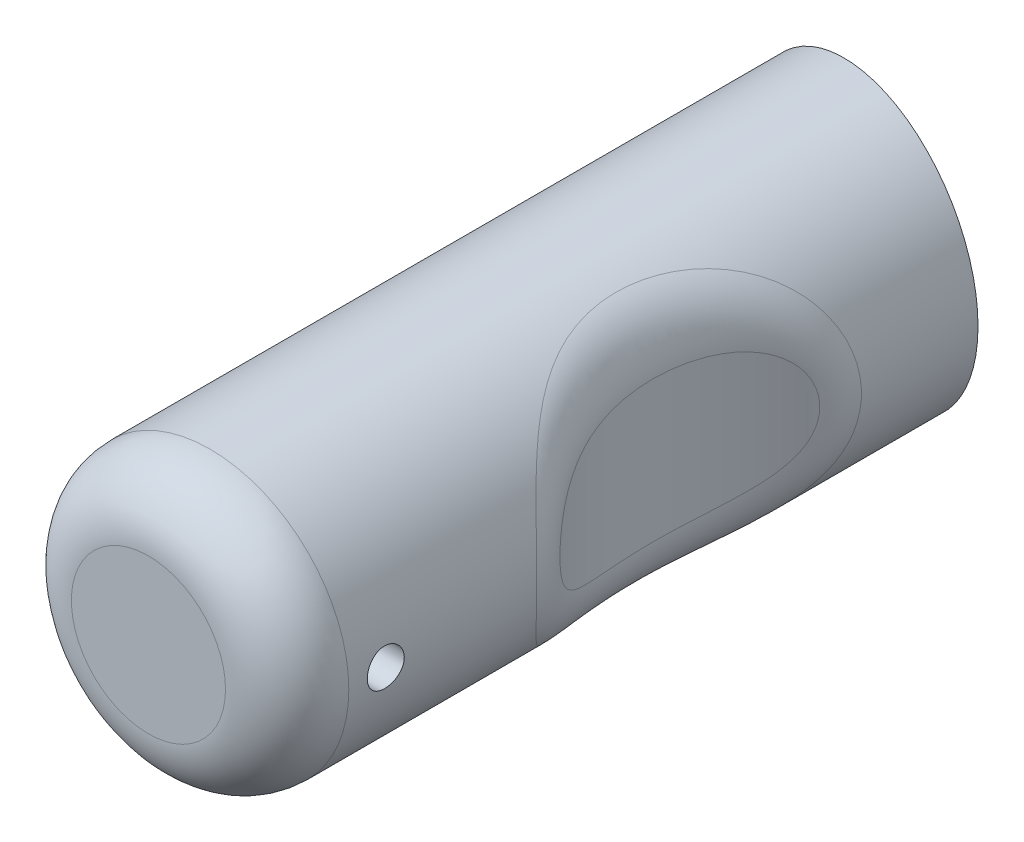
SolidWorks part; units mm, degrees
ref_plane "Front Plane" through (0, 0, 0) normal (0, 0, 1) x (1, 0, 0)
ref_plane "Top Plane" through (0, 0, 0) normal (0, 1, 0) x (1, 0, 0)
ref_plane "Right Plane" through (0, 0, 0) normal (1, 0, 0) x (0, 0, -1)
sketch "Sketch1" plane through (0, 0, 0) normal (0, 0, 1) x (1, 0, 0)
  circle A0 centre (0, 0) radius 22.5
  dimension "D1" = 45
extrude "Boss-Extrude1" add sketch "Sketch1" along normal blind 120
sketch "Sketch5" plane through (0, 0, 0) normal (0, 1, 0) x (1, 0, 0)
  line L0 (0, 0) -> (0, -120) construction
  line L1 (-22.5, -120) -> (22.5, -120) construction
  circle A0 centre (-30, -21.8566) radius 10
  circle A1 centre (-30, -61.8566) radius 10
  circle A2 centre (-30, -41.8566) radius 10
  circle A3 centre (-30, -81.8566) radius 10
  circle A4 centre (55, -53.1749) radius 40
  dimension "D1" = 20
  dimension "D3" = 20
  dimension "D4" = 20
  dimension "D5" = 55
  dimension "D6" = 30
  dimension "D2" = 20
extrude "Cut-Extrude5" cut sketch "Sketch5" against normal blind 124 and the other way blind 124 contours A2 | A0 | A1 | A3 | A4 region at (-30, 0, 21.8566) region at (-30, 0, 81.8566) region at (-30, 0, 61.8566) region at (-30, 0, 41.8566) region at (55, 0, 53.1749)
fillet "Fillet6" radius 10 1 edges at (22.5, 0, 120)
sketch "Sketch6" plane through (0, 0, 0) normal (0, 0, -1) x (-1, 0, 0)
  circle A0 centre (0, 0) radius 7.5
  dimension "D1" = 15
sketch "Sketch7" plane through (0, 0, 0) normal (1, 0, 0) x (0, 0, -1)
  line L0 (0, 0) -> (-110, 0) construction
  line L1 (-110, -22.5) -> (-110, 22.5) construction
  line L2 (-104, 22.5) -> (-104, -3) construction
  line L3 (0, 22.5) -> (-110, 22.5) construction
  circle A0 centre (-104, 0) radius 3
  dimension "D1" = 6
  dimension "D2" = 6
extrude "Cut-Extrude9" cut sketch "Sketch7" along normal blind 110
fillet "Fillet8" radius 10 5 edges at (22.3173, 2.8617, 30.1133) (-22.1484, -3.9619, 75.6636) (-22.1484, -3.9619, 55.6636) (-22.1484, -3.9619, 35.6636) (-22.1484, -3.9619, 15.6636)
sketch "Sketch9" plane through (0, 0, 0) normal (0, 1, 0) x (1, 0, 0)
  line L0 (-55.0338, 5.7366) -> (-53.8437, 18.2687)
  line L1 (33.1273, -9.8086) -> (77.5, -17.6327)
  line L3 (-53.8437, 18.2687) -> (77.5, 7.5385)
  line L4 (77.5, 7.5385) -> (77.5, -17.6327)
  line L5 (77.5, -17.6327) -> (33.1273, -9.8086) construction
  line L6 (33.1273, -9.8086) -> (-55.0338, 5.7366)
extrude "Cut-Extrude11" cut sketch "Sketch9" against normal through all and the other way through all
extrude "Boss-Extrude2" add sketch "Sketch6" along normal blind 10 and the other way blind 23 contours A0
sketch "Sketch12" plane through (0, 0, 0) normal (0, 1, 0) x (1, 0, 0)
  line L0 (33.151, 4.9718) -> (43.2416, 4.9718)
  line L1 (43.2416, 4.9718) -> (33.151, 4.9718)
  line L3 (-24.7372, 4.9718) -> (39.8348, -6.414)
  line L4 (-24.7372, 4.9718) -> (-24.7372, 13.5753)
  line L5 (-24.7372, 13.5753) -> (33.151, 12.6194)
  line L6 (33.151, 12.6194) -> (33.151, -5.2355)
  dimension "D1" = 10
extrude "Cut-Extrude12" cut sketch "Sketch12" against normal blind 33 and the other way blind 33 contours L6 L5 L4 L3 region at (7.5804, 0, -6.1575)
